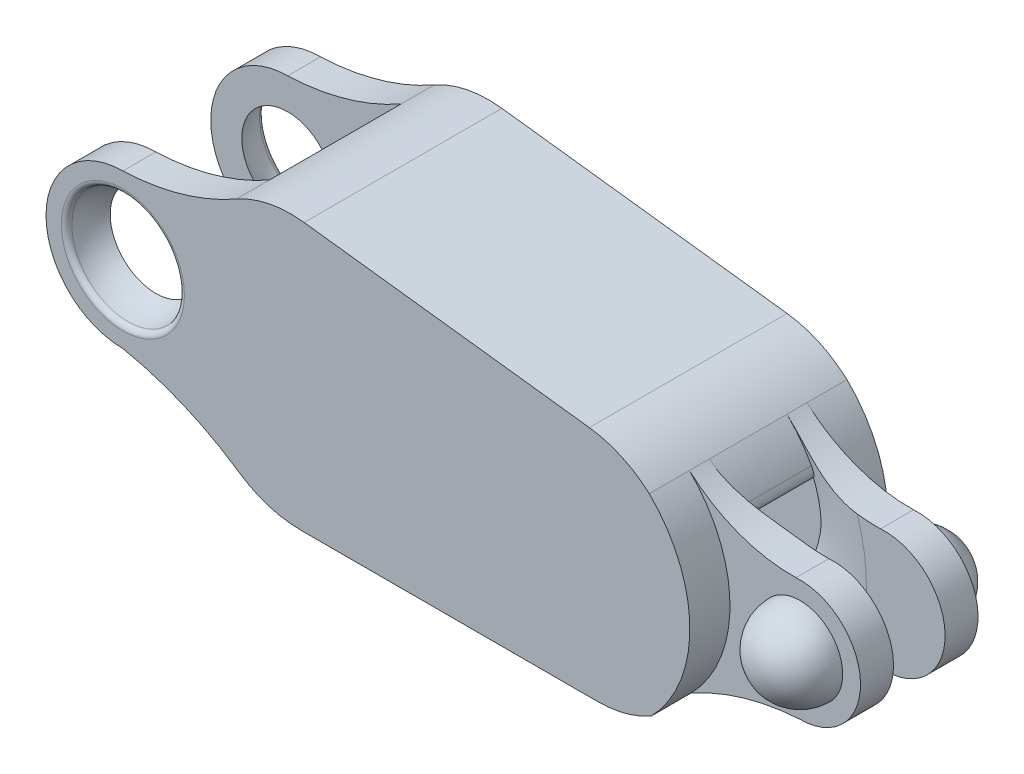
SolidWorks part; units mm, degrees
other "Markup1"
sketch "Sketch11" plane through (-101.0368, 18.7023, -18.225) normal (-0.4615, 0.8857, -0.0515) x (-0.095, 0.0083, 0.9954)
material "PBT General Purpose"
ref_plane "Front Plane" through (0, 0, 0) normal (0, 0, 1) x (1, 0, 0)
ref_plane "Top Plane" through (0, 0, 0) normal (0, 1, 0) x (1, 0, 0)
ref_plane "Right Plane" through (0, 0, 0) normal (1, 0, 0) x (0, 0, -1)
sketch "Sketch2" plane through (0, 0, 0) normal (0, 0, 1) x (1, 0, 0)
  line L0 (-11.9741, 10.1961) -> (-24.9243, 11.7862)
  line L1 (-24.407, -6.1642) -> (-10.737, -6.1642)
  line L2 (-24.407, -6.1642) -> (-114.7225, -6.1642) construction
  line L3 (-24.9243, 11.7862) -> (-117.2343, 23.1205) construction
  line L4 (-117.2343, 23.1205) -> (-106.132, 23.1205) construction
  line L5 (-36.0368, 3.4932) -> (-94.0368, 3.4932) construction
  line L6 (-94.0368, -6.1642) -> (-94.0368, 20.2722) construction
  line L7 (-51.5724, 15.0582) -> (-77.5359, 18.2461)
  line L8 (-50.839, -6.1642) -> (-77.8113, -6.1642)
  circle A0 centre (0, 0) radius 2.2523
  arc A1 (-7.2917, -5.5162) -> (-6.5963, 7.6571) centre (-13.5307, 1.4181) ccw
  arc A2 (-6.5963, 7.6571) -> (-11.9741, 10.1961) centre (-13.1299, 0.7835) ccw
  arc A3 (-24.9243, 11.7862) -> (-30.037, 10.9919) centre (-26.08, 2.3735) ccw
  circle A4 centre (-36.0368, 3.4932) radius 5.5
  arc A5 (-36.0368, -2.0068) -> (-45.9623, -4.8945) centre (-34.7281, -25.0064) ccw
  arc A6 (-36.0368, 8.9932) -> (-46.1141, 12.577) centre (-36.7092, 23.0627) cw
  arc A7 (-29.3592, -4.7684) -> (-24.407, -6.1642) centre (-24.407, 3.3192) ccw
  arc A8 (-10.737, -6.1642) -> (-7.2917, -5.5162) centre (-10.737, 3.3192) ccw
  arc A9 (-7.2917, -5.5162) -> (-6.5963, 7.6571) centre (-13.5307, 1.4181) ccw
  arc A10 (0, -3.7933) -> (-7.2917, -5.5162) centre (2.4771, -30.5689) ccw
  arc A11 (0, -3.7933) -> (0.6007, 3.7455) centre (0, 0) ccw
  arc A12 (-1.6071, 4.3814) -> (0.6007, 3.7455) centre (2.1025, 13.1092) ccw
  arc A13 (-6.5963, 7.6571) -> (-1.6071, 4.3814) centre (4.9468, 19.8012) ccw
  circle A14 centre (-36.0368, 3.4932) radius 3.875
  circle A16 centre (-94.0368, 7.054) radius 5
  circle A17 centre (-94.0368, 7.054) radius 7
  arc A18 (-94.0368, 14.054) -> (-83.7049, 17.0094) centre (-94.9283, 36.7082) ccw
  arc A19 (-94.0368, 0.054) -> (-83.4637, -4.4134) centre (-99.7159, -28.1321) cw
  arc A20 (-46.1141, 12.577) -> (-51.5724, 15.0582) centre (-52.7911, 5.1327) ccw
  arc A21 (-83.7049, 17.0094) -> (-77.5359, 18.2461) centre (-78.7546, 8.3206) cw
  arc A22 (-77.8113, -6.1642) -> (-83.4637, -4.4134) centre (-77.8113, 3.8358) cw
  arc A23 (-45.9623, -4.8945) -> (-50.839, -6.1642) centre (-50.839, 3.8358) cw
  point P49 (-47.9821, 14.6174)
  point P52 (-81.1655, 18.6918)
  point P55 (-81.1655, -6.1642)
  point P58 (-47.9821, -6.1642)
  dimension "D1" = 7.75
  dimension "D4" = 11
  dimension "D5" = 10
  dimension "D6" = 2
  dimension "D7" = 10
  dimension "D2" = 7
  dimension "D3" = 58
extrude "Boss-Extrude1" add sketch "Sketch2" against normal blind 18 contours A23 A5 A4 A6 A20 L7 A21 A18 A17 A19 A22 L8 | A4 | A17 region at (-65.6327, 5.2362, 0)
sketch "Sketch3" plane through (0, 0, 0) normal (0, 0, 1) x (1, 0, 0)
  line L0 (-51.938, 12.0806) -> (-77.9015, 15.2685)
  line L1 (-77.8113, -3.1642) -> (-50.839, -3.1642)
  line L2 (-51.5724, 15.0582) -> (-77.5359, 18.2461)
  line L3 (-77.8113, -6.1642) -> (-50.839, -6.1642)
  line L4 (-51.5724, 15.0582) -> (-77.5359, 18.2461)
  line L5 (-77.8113, -6.1642) -> (-50.839, -6.1642)
  arc A0 (-77.9015, 15.2685) -> (-82.2198, 14.4027) centre (-78.7546, 8.3206) ccw
  arc A1 (-93.9878, 11.0537) -> (-82.2198, 14.4027) centre (-94.9283, 36.7082) ccw
  arc A2 (-93.9878, 11.0537) -> (-93.7863, 3.0618) centre (-94.0368, 7.054) ccw
  arc A3 (-81.768, -1.9387) -> (-93.7863, 3.0618) centre (-99.7159, -28.1321) ccw
  arc A4 (-81.768, -1.9387) -> (-77.8113, -3.1642) centre (-77.8113, 3.8358) ccw
  arc A5 (-50.839, -3.1642) -> (-47.4253, -2.2754) centre (-50.839, 3.8358) ccw
  arc A6 (-36.103, 0.9941) -> (-47.4253, -2.2754) centre (-34.7281, -25.0064) ccw
  arc A7 (-36.103, 0.9941) -> (-36.2626, 5.983) centre (-36.0368, 3.4932) ccw
  arc A8 (-48.1172, 10.3437) -> (-36.2626, 5.983) centre (-36.7092, 23.0627) ccw
  arc A9 (-48.1172, 10.3437) -> (-51.938, 12.0806) centre (-52.7911, 5.1327) ccw
  arc A10 (-50.839, -6.1642) -> (-45.9623, -4.8945) centre (-50.839, 3.8358) ccw
  arc A11 (-36.0368, -2.0068) -> (-45.9623, -4.8945) centre (-34.7281, -25.0064) ccw
  arc A12 (-36.0368, -2.0068) -> (-36.4143, 8.9803) centre (-36.0368, 3.4932) ccw
  arc A13 (-46.1141, 12.577) -> (-36.4143, 8.9803) centre (-36.7092, 23.0627) ccw
  arc A14 (-46.1141, 12.577) -> (-51.5724, 15.0582) centre (-52.7911, 5.1327) ccw
  arc A15 (-77.5359, 18.2461) -> (-83.7049, 17.0094) centre (-78.7546, 8.3206) ccw
  arc A16 (-94.0368, 14.054) -> (-83.7049, 17.0094) centre (-94.9283, 36.7082) ccw
  arc A17 (-94.0368, 14.054) -> (-94.0368, 0.054) centre (-94.0368, 7.054) ccw
  arc A18 (-83.4637, -4.4134) -> (-94.0368, 0.054) centre (-99.7159, -28.1321) ccw
  arc A19 (-83.4637, -4.4134) -> (-77.8113, -6.1642) centre (-77.8113, 3.8358) ccw
  arc A20 (-50.839, -6.1642) -> (-45.9623, -4.8945) centre (-50.839, 3.8358) ccw
  arc A21 (-36.0368, -2.0068) -> (-45.9623, -4.8945) centre (-34.7281, -25.0064) ccw
  arc A22 (-36.0368, -2.0068) -> (-36.4143, 8.9803) centre (-36.0368, 3.4932) ccw
  arc A23 (-46.1141, 12.577) -> (-36.4143, 8.9803) centre (-36.7092, 23.0627) ccw
  arc A24 (-46.1141, 12.577) -> (-51.5724, 15.0582) centre (-52.7911, 5.1327) ccw
  arc A25 (-77.5359, 18.2461) -> (-83.7049, 17.0094) centre (-78.7546, 8.3206) ccw
  arc A26 (-94.0368, 14.054) -> (-83.7049, 17.0094) centre (-94.9283, 36.7082) ccw
  arc A27 (-94.0368, 14.054) -> (-94.0368, 0.054) centre (-94.0368, 7.054) ccw
  arc A28 (-83.4637, -4.4134) -> (-94.0368, 0.054) centre (-99.7159, -28.1321) ccw
  arc A29 (-83.4637, -4.4134) -> (-77.8113, -6.1642) centre (-77.8113, 3.8358) ccw
  arc A30 (-46.1141, 12.577) -> (-45.9623, -4.8945) centre (-54.774, 3.7654) cw
  arc A31 (-83.7049, 17.0094) -> (-83.4637, -4.4134) centre (-72.8729, 6.4186) ccw
  arc M26 (-45.9623, -4.8945) -> (-36.0368, -2.0068) centre (-34.7281, -25.0064) cw
  arc M27 (-36.0368, -2.0068) -> (-36.4143, 8.9803) centre (-36.0368, 3.4932) ccw
  arc M28 (-36.4143, 8.9803) -> (-46.1141, 12.577) centre (-36.7092, 23.0627) cw
  arc M32 (-83.7049, 17.0094) -> (-94.0368, 14.054) centre (-94.9283, 36.7082) cw
  arc M33 (-94.0368, 14.054) -> (-94.0368, 0.054) centre (-94.0368, 7.054) ccw
  arc M34 (-94.0368, 0.054) -> (-83.4637, -4.4134) centre (-99.7159, -28.1321) cw
  dimension "D1" = 0
  dimension "D2" = 3
extrude "Cut-Extrude2" cut sketch "Sketch3" against normal blind 12 from offset 3 contours A31 A3 A2 A1 M32 M33 M34 | A1 A0 L0 A9 A8 A7 A6 A5 L1 A4 A3 A2 region at (-90.4025, 11.7201, 0) offset against normal yes
fillet "Fillet1" radius 1 2 edges at (-87.0069, 0.9661, -9) (-86.8111, 12.3535, -9)
extrude "Cut-Extrude3" cut sketch "Sketch3<4>" against normal through all and the other way through all contours A6 A30 A8 A7 M26 M27 M28 | A8 A30 A6 A7 region at (-43.9448, 10.1846, 0) region at (-38.5956, 3.4114, 0)
sketch "Sketch3<4>" plane through (0, 0, 0) normal (0, 0, 1) x (1, 0, 0) same geometry as "Sketch3"
extrude "Boss-Extrude2" add sketch "Sketch3<5>" against normal blind 3 from offset 3.65 contours A6 A30 A8 A7 M26 M27 M28 | A8 A30 A6 A7 region at (-43.9448, 10.1846, 0) region at (-38.5956, 3.4114, 0) offset against normal yes
sketch "Sketch3<5>" plane through (0, 0, 0) normal (0, 0, 1) x (1, 0, 0) same geometry as "Sketch3"
sketch "Sketch6" plane through (0, 0, 0) normal (0, 0, 1) x (1, 0, 0)
  line L0 (-51.938, 12.0806) -> (-77.9015, 15.2685)
  line L1 (-77.8113, -3.1642) -> (-50.839, -3.1642)
  line L2 (-51.5724, 15.0582) -> (-77.5359, 18.2461)
  line L3 (-77.8113, -6.1642) -> (-50.839, -6.1642)
  line L4 (-56.1483, 15.62) -> (-77.5359, 18.2461)
  line L5 (-77.8113, -6.1642) -> (-55.9501, -6.1642)
  line L6 (-51.5724, 15.0582) -> (-77.5359, 18.2461) construction
  line L7 (-77.8113, -6.1642) -> (-50.839, -6.1642) construction
  arc A0 (-47.8009, -2.4706) -> (-48.1673, 10.3883) centre (-54.774, 3.7654) ccw
  arc A1 (-48.1673, 10.3883) -> (-51.938, 12.0806) centre (-52.7911, 5.1327) ccw
  arc A2 (-77.9015, 15.2685) -> (-82.2198, 14.4027) centre (-78.7546, 8.3206) ccw
  arc A3 (-93.9878, 11.0537) -> (-82.2198, 14.4027) centre (-94.9283, 36.7082) ccw
  arc A4 (-93.9878, 11.0537) -> (-93.7863, 3.0618) centre (-94.0368, 7.054) ccw
  arc A5 (-81.768, -1.9387) -> (-93.7863, 3.0618) centre (-99.7159, -28.1321) ccw
  arc A6 (-46.1141, 12.577) -> (-36.4143, 8.9803) centre (-36.7092, 23.0627) ccw
  arc A7 (-42.8872, 7.1333) -> (-46.1141, 12.577) centre (-54.774, 3.7654) ccw
  arc A8 (-45.9623, -4.8945) -> (-46.1141, 12.577) centre (-54.774, 3.7654) ccw
  arc A9 (-46.1141, 12.577) -> (-51.5724, 15.0582) centre (-52.7911, 5.1327) ccw
  arc A10 (-77.5359, 18.2461) -> (-83.7049, 17.0094) centre (-78.7546, 8.3206) ccw
  arc A11 (-94.0368, 14.054) -> (-83.7049, 17.0094) centre (-94.9283, 36.7082) ccw
  arc A12 (-94.0368, 14.054) -> (-94.0368, 0.054) centre (-94.0368, 7.054) ccw
  arc A13 (-83.4637, -4.4134) -> (-94.0368, 0.054) centre (-99.7159, -28.1321) ccw
  arc A14 (-83.4637, -4.4134) -> (-77.8113, -6.1642) centre (-77.8113, 3.8358) ccw
  arc A15 (-50.839, -6.1642) -> (-45.9623, -4.8945) centre (-50.839, 3.8358) ccw
  arc A16 (-45.9623, -4.8945) -> (-46.1141, 12.577) centre (-54.774, 3.7654) ccw
  arc A17 (-46.1141, 12.577) -> (-51.5724, 15.0582) centre (-52.7911, 5.1327) ccw
  arc A18 (-77.5359, 18.2461) -> (-83.7049, 17.0094) centre (-78.7546, 8.3206) ccw
  arc A19 (-94.0368, 14.054) -> (-83.7049, 17.0094) centre (-94.9283, 36.7082) ccw
  arc A20 (-94.0368, 14.054) -> (-94.0368, 0.054) centre (-94.0368, 7.054) ccw
  arc A21 (-83.4637, -4.4134) -> (-94.0368, 0.054) centre (-99.7159, -28.1321) ccw
  arc A22 (-83.4637, -4.4134) -> (-77.8113, -6.1642) centre (-77.8113, 3.8358) ccw
  arc A23 (-50.839, -6.1642) -> (-45.9623, -4.8945) centre (-50.839, 3.8358) ccw
  arc A24 (-43.1291, -0.3621) -> (-42.8872, 7.1333) centre (-54.774, 3.7654) ccw
  arc A25 (-45.9623, -4.8945) -> (-43.1291, -0.3621) centre (-54.774, 3.7654) ccw
  arc A26 (-36.0368, -2.0068) -> (-45.9623, -4.8945) centre (-34.7281, -25.0064) ccw
  arc A27 (-36.0368, -2.0068) -> (-36.4143, 8.9803) centre (-36.0368, 3.4932) ccw
  arc A28 (-46.1141, 12.577) -> (-36.4143, 8.9803) centre (-36.7092, 23.0627) ccw
  arc A29 (-42.8872, 7.1333) -> (-46.1141, 12.577) centre (-54.774, 3.7654) ccw
  arc A30 (-43.1291, -0.3621) -> (-42.8872, 7.1333) centre (-54.774, 3.7654) ccw
  arc A31 (-45.9623, -4.8945) -> (-43.1291, -0.3621) centre (-54.774, 3.7654) ccw
  arc A32 (-36.0368, -2.0068) -> (-45.9623, -4.8945) centre (-34.7281, -25.0064) ccw
  arc A33 (-36.0368, -2.0068) -> (-36.4143, 8.9803) centre (-36.0368, 3.4932) ccw
  arc A34 (-81.768, -1.9387) -> (-77.8113, -3.1642) centre (-77.8113, 3.8358) ccw
  arc A35 (-50.839, -3.1642) -> (-47.8009, -2.4706) centre (-50.839, 3.8358) ccw
  arc A36 (-48.1673, 10.3883) -> (-49.5554, 11.938) centre (-35.082, 23.5059) cw
  arc A37 (-49.5554, 11.938) -> (-56.1483, 15.62) centre (-57.367, 5.6946) ccw
  arc A38 (-47.8009, -2.4706) -> (-49.0708, -3.422) centre (-44.3392, -8.4141) ccw
  arc A39 (-55.9501, -6.1642) -> (-49.0708, -3.422) centre (-55.9501, 3.8358) ccw
  arc M27 (-45.9623, -4.8945) -> (-46.1141, 12.577) centre (-54.774, 3.7654) ccw
  arc M28 (-46.1141, 12.577) -> (-51.5724, 15.0582) centre (-52.7911, 5.1327) ccw
  line M29 (-51.5724, 15.0582) -> (-77.5359, 18.2461)
  line M35 (-77.8113, -6.1642) -> (-50.839, -6.1642)
  arc M36 (-50.839, -6.1642) -> (-45.9623, -4.8945) centre (-50.839, 3.8358) ccw
  dimension "D4" = 10
  dimension "D5" = 10
  dimension "D1" = 0
  dimension "D2" = 0
  dimension "D3" = 3
extrude "Boss-Extrude3" add sketch "Sketch6" against normal up to surface (6.65 mm away) from offset 2 contours A39 A16 A37 A36 A0 A38 M35 M36 M27 M28 M29 region at (-48.6914, 11.3154, 0) up to face at (-40.6966, 3.55, -6.65) offset against normal yes
ref_plane "Plane1" through (0, 0, -9) normal (0, 0, -1) x (-1, 0, 0)
mirror "Mirror1" about plane through (0, 0, -9) normal (0, 0, -1) of "Boss-Extrude3", "Boss-Extrude2"
fillet "Fillet2" radius 10 2 edges at (-45.4231, 4.0318, -6.65) (-45.4231, 4.0318, -11.35)
fillet "Fillet3" radius 1 2 edges at (-43.1291, -0.3621, -9) (-42.8872, 7.1333, -9)
sketch "Sketch7" plane through (0, 0, -14.35) normal (0, 0, -1) x (-1, 0, 0)
  line L0 (36.0368, -2.0068) -> (36.0368, 12.1685)
  circle A0 centre (36.0368, 3.4932) radius 3.875
  arc A4 (36.4143, 8.9803) -> (46.1141, 12.577) centre (36.7092, 23.0627) ccw
  arc A5 (36.4143, 8.9803) -> (36.0368, -2.0068) centre (36.0368, 3.4932) ccw
  arc A6 (45.9623, -4.8945) -> (36.0368, -2.0068) centre (34.7281, -25.0064) ccw
  arc A7 (46.1141, 12.577) -> (45.9623, -4.8945) centre (54.774, 3.7654) ccw
  arc A8 (36.4143, 8.9803) -> (46.1141, 12.577) centre (36.7092, 23.0627) ccw
  arc A9 (36.4143, 8.9803) -> (36.0368, -2.0068) centre (36.0368, 3.4932) ccw
  arc A10 (45.9623, -4.8945) -> (36.0368, -2.0068) centre (34.7281, -25.0064) ccw
  arc A11 (46.1141, 12.577) -> (45.9623, -4.8945) centre (54.774, 3.7654) ccw
  dimension "D2" = 7.75
  dimension "D1" = 0
revolve "Revolve1" add sketch "Sketch7" angle 180 about L0 region at (-34.3922, 3.4932, -14.35)
mirror "Mirror2" about plane through (0, 0, -9) normal (0, 0, -1) of "Revolve1"
sketch "Sketch8" plane through (0, 0, -3) normal (0, 0, -1) x (-1, 0, 0)
  line L0 (94.0368, 0.054) -> (94.0368, 18.7023)
  line L2 (50.839, -3.1642) -> (77.8113, -3.1642)
  line L3 (77.9015, 15.2685) -> (51.938, 12.0806)
  line L4 (50.839, -3.1642) -> (77.8113, -3.1642)
  line L5 (77.9015, 15.2685) -> (51.938, 12.0806)
  circle A0 centre (94.0368, 7.054) radius 5.125
  arc A14 (48.1673, 10.3883) -> (47.8009, -2.4706) centre (54.774, 3.7654) ccw
  arc A15 (47.8009, -2.4706) -> (50.839, -3.1642) centre (50.839, 3.8358) ccw
  arc A16 (77.8113, -3.1642) -> (81.768, -1.9387) centre (77.8113, 3.8358) ccw
  arc A17 (84.268, -0.3907) -> (81.768, -1.9387) centre (99.7159, -28.1321) ccw
  arc A18 (85.5942, -1.8074) -> (84.268, -0.3907) centre (84.7545, -1.2644) ccw
  arc A19 (83.4637, -4.4134) -> (85.5942, -1.8074) centre (72.8729, 6.4186) ccw
  arc A20 (94.0368, 0.054) -> (83.4637, -4.4134) centre (99.7159, -28.1321) ccw
  arc A21 (94.0368, 0.054) -> (94.0368, 14.054) centre (94.0368, 7.054) ccw
  arc A22 (83.7049, 17.0094) -> (94.0368, 14.054) centre (94.9283, 36.7082) ccw
  arc A23 (85.4631, 14.8438) -> (83.7049, 17.0094) centre (72.8729, 6.4186) ccw
  arc A24 (84.2147, 13.3789) -> (85.4631, 14.8438) centre (84.6321, 14.2876) ccw
  arc A25 (82.2198, 14.4027) -> (84.2147, 13.3789) centre (94.9283, 36.7082) ccw
  arc A26 (82.2198, 14.4027) -> (77.9015, 15.2685) centre (78.7546, 8.3206) ccw
  arc A27 (51.938, 12.0806) -> (48.1673, 10.3883) centre (52.7911, 5.1327) ccw
  arc A28 (48.1673, 10.3883) -> (47.8009, -2.4706) centre (54.774, 3.7654) ccw
  arc A29 (47.8009, -2.4706) -> (50.839, -3.1642) centre (50.839, 3.8358) ccw
  arc A30 (77.8113, -3.1642) -> (81.768, -1.9387) centre (77.8113, 3.8358) ccw
  arc A31 (84.268, -0.3907) -> (81.768, -1.9387) centre (99.7159, -28.1321) ccw
  arc A32 (85.5942, -1.8074) -> (84.268, -0.3907) centre (84.7545, -1.2644) ccw
  arc A33 (83.4637, -4.4134) -> (85.5942, -1.8074) centre (72.8729, 6.4186) ccw
  arc A34 (94.0368, 0.054) -> (83.4637, -4.4134) centre (99.7159, -28.1321) ccw
  arc A35 (94.0368, 0.054) -> (94.0368, 14.054) centre (94.0368, 7.054) ccw
  arc A36 (83.7049, 17.0094) -> (94.0368, 14.054) centre (94.9283, 36.7082) ccw
  arc A37 (85.4631, 14.8438) -> (83.7049, 17.0094) centre (72.8729, 6.4186) ccw
  arc A38 (84.2147, 13.3789) -> (85.4631, 14.8438) centre (84.6321, 14.2876) ccw
  arc A39 (82.2198, 14.4027) -> (84.2147, 13.3789) centre (94.9283, 36.7082) ccw
  arc A40 (82.2198, 14.4027) -> (77.9015, 15.2685) centre (78.7546, 8.3206) ccw
  arc A41 (51.938, 12.0806) -> (48.1673, 10.3883) centre (52.7911, 5.1327) ccw
  dimension "D2" = 10.25
  dimension "D1" = 0
sketch "Sketch9" plane through (0, 0, 0) normal (0, 0, 1) x (1, 0, 0)
  line L0 (-94.0368, 0.054) -> (-94.0368, 18.7023) construction
  line L1 (-94.0368, 1.929) -> (-94.0368, 12.179)
  arc A0 (-94.0368, 1.929) -> (-94.0368, 12.179) centre (-94.0368, 7.054) ccw
  circle A1 centre (-94.0368, 7.054) radius 5.125 construction
  point P6 (-94.0368, 7.054)
  dimension "D1" = 5.125
revolve "Cut-Revolve12" cut sketch "Sketch9" angle 360 about L1
sketch "Sketch10" plane through (0, 0, -18) normal (0, 0, -1) x (-1, 0, 0)
  line L0 (94.0368, 0.054) -> (94.0368, 18.7023) construction
  line L1 (94.0368, 1.9147) -> (94.0368, 12.1932)
  arc A0 (94.0368, 12.1932) -> (94.0368, 1.9147) centre (94.0368, 7.054) ccw
revolve "Cut-Revolve13" cut sketch "Sketch10" angle 360 about L1
fillet "Fillet4" radius 0.5 1 edges at (-88.8976, 7.054, -18)
fillet "Fillet5" radius 0.5 1 edges at (-88.9118, 7.054, 0)
